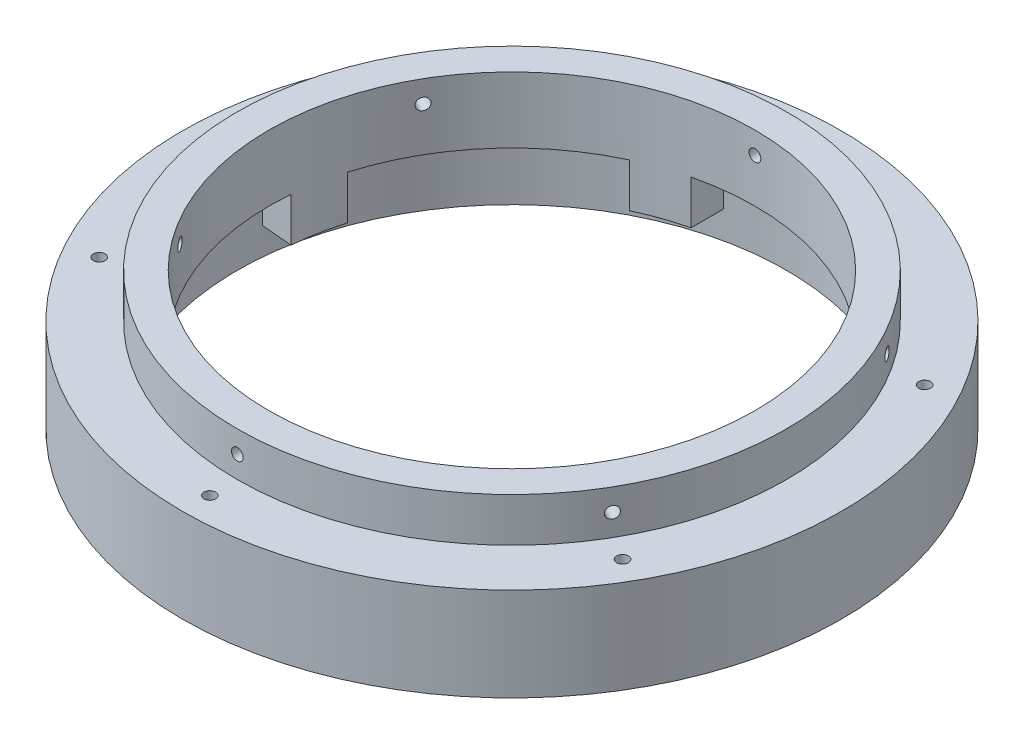
SolidWorks part; units mm, degrees
ref_plane "Front Plane" through (0, 0, 0) normal (0, 0, 1) x (1, 0, 0)
ref_plane "Top Plane" through (0, 0, 0) normal (0, 1, 0) x (1, 0, 0)
ref_plane "Right Plane" through (0, 0, 0) normal (1, 0, 0) x (0, 0, -1)
sketch "Sketch1" plane through (0, 0, 0) normal (0, 1, 0) x (1, 0, 0)
  circle A0 centre (0, 0) radius 63.5
  circle A1 centre (0, 0) radius 76.2
  circle A2 centre (0, 0) radius 56.1975
  dimension "D1" = 152.4
  dimension "D3" = 112.395
  dimension "D2" = 12.7
extrude "Boss-Extrude1" add sketch "Sketch1" along normal blind 15.24 contours A0 A2 region at (-61.7039, 0, 0)
extrude "Boss-Extrude2" add sketch "Sketch1<4>" along normal blind 5.08 and the other way blind 16.51 contours A1 A0 region at (-74.0447, 0, 0)
sketch "Sketch1<4>" plane through (0, 0, 0) normal (0, 1, 0) x (1, 0, 0) same geometry as "Sketch1"
sketch "Sketch3" plane through (0, -16.51, 0) normal (0, -1, 0) x (1, 0, 0)
  line L0 (0, 0) -> (-68.319, 5.9771) construction
  line L1 (0, 0) -> (0, 69.85) construction
  line L2 (0, 0) -> (48.9804, 58.3726)
  line L3 (0, 0) -> (13.232, 75.0424)
  line L4 (-13.2113, -54.6225) -> (-13.2113, -60.147)
  line L5 (13.2113, -54.6225) -> (13.2113, -60.147)
  line L6 (-13.2113, -60.147) -> (13.2113, -60.147)
  line L7 (-13.2113, -60.147) -> (-13.2113, -62.1105)
  line L8 (-23.7501, -50.9322) -> (-26.8363, -57.5505)
  line L9 (0, 0) -> (-23.7501, -50.9322) construction
  circle A0 centre (-68.319, 5.9771) radius 3.9561
  circle A1 centre (0, 69.85) radius 1.3589
  circle A2 centre (0, 0) radius 76.2 construction
  circle A5 centre (0, 0) radius 56.1975 construction
  circle A6 centre (0, 0) radius 63.5 construction
  arc A7 (-26.8363, -57.5505) -> (-13.2113, -62.1105) centre (0, 0) ccw
  arc A9 (-23.7501, -50.9322) -> (-13.2113, -54.6225) centre (0, 0) ccw
  point P0 (0, -60.147)
  dimension "D4" = 7.9121
  dimension "D5" = 2.7178
  dimension "D2" = 85
  dimension "D3" = 69.85
  dimension "D6" = 30
  dimension "D7" = 10
  dimension "D9" = 26.4227
  dimension "D8" = 5.5245
  dimension "D10" = 25
extrude "Cut-Extrude1" cut sketch "Sketch3" against normal blind 15.24 contours A0
extrude "Cut-Extrude2" cut sketch "Sketch3<3>" against normal through all contours A1 | A1 region at (0, -16.51, 69.85)
sketch "Sketch3<3>" plane through (0, -16.51, 0) normal (0, -1, 0) x (1, 0, 0) same geometry as "Sketch3"
pattern_circular "CirPattern1" count 3 over 360 about axis through (0, -16.51, 0) along (0, 1, 0) of "Cut-Extrude1"
pattern_circular "CirPattern2" count 6 over 360 about axis through (0, -16.51, 0) along (0, 1, 0) of "Cut-Extrude2"
ref_plane "Plane1" through (0, 0, 76.2) normal (0, 0, 1) x (1, 0, 0)
sketch "Sketch5" plane through (0, 0, 76.2) normal (0, 0, 1) x (1, 0, 0)
  line L0 (0, -16.51) -> (0, 10.16) construction
  line L1 (-1.3589, -16.51) -> (1.3589, -16.51) construction
  circle A0 centre (0, 10.16) radius 1.3589
  dimension "D2" = 2.7178
  dimension "D1" = 26.67
extrude "Cut-Extrude3" cut sketch "Sketch5" against normal up to surface (132.3811 mm away) up to face at (0, 15.24, 56.1975)
extrude "Boss-Extrude3" add sketch "Sketch3<11>" along normal blind 10.16 from surface contours L4 A9 L8 A7 L7 starting at face at (0, 0, 56.1975)
sketch "Sketch3<11>" plane through (0, -16.51, 0) normal (0, -1, 0) x (1, 0, 0) same geometry as "Sketch3"
pattern_circular "CirPattern3" count 6 over 360 about axis through (0, 15.24, 0) along (0, 1, 0) of "Cut-Extrude3", "Boss-Extrude3"
equation "\"Middle Coupler Inner Daimeter\"= 3.875in"
equation "\"Middle Coupler  Wall Thickness\" = 0.25in"
equation "\"Middle Coupler Bottom Thickness\"= 0.2in"
equation "\"Bearing Rail Offset\"= 0.45in"
equation "\"3-56 UNF Tap\"= 0.089in"
equation "\"3-48 Tap\"= 0.079in"
equation "\"3-56 UNF Clearance\"= 0.104in"
equation "\"3-48 Clearance\" = 0.104in"
equation "\"Ball Bearing Distance\"= 0.03in"
equation "\"TCA Outer Diameter\" = 6in"
equation "\"Interstage Aeroframe Wall Thickness\" = 0.072in"
equation "\"Compression Spring OD\"= 0.42in"
equation "\"10-24 Tap\"= 0.157in"
equation "\"10-24 Clearance\"= 0.196in"
equation "\"Lower Stage Fuselage Wall Thickness\" = 0.25in"
equation "\"6-32 Tap\" = 0.107in"
equation "\"6-32 Clearance\" = 0.144"
equation "\"1/4-20 Tap\" = 0.201in"
equation "\"12-24 Tap\" = 0.177in"
equation "\"D1@Sketch1\"=\"TCA Outer Diameter\""
equation "\"D5@Sketch3\"=\"6-32 Tap\""
equation "\"D1@Sketch5\"=\"D2@Boss-Extrude2\"+(\"D1@Boss-Extrude2\"+\"D1@Boss-Extrude1\")/2"
equation "\"D2@Sketch5\"=\"6-32 Tap\""
equation "\"D8@Sketch3\"=3/16+0.03"
equation "\"D3@Sketch1\"=\"Middle Coupler Inner Daimeter\" + 0.55"
